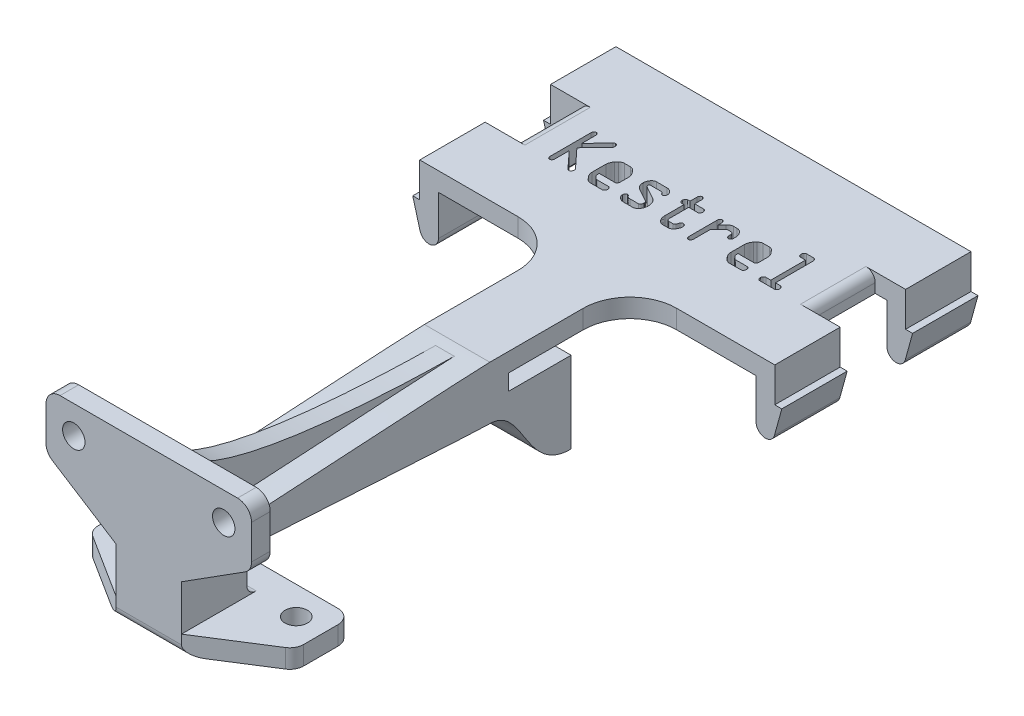
SolidWorks part; units mm, degrees
ref_plane "Front Plane" through (0, 0, 0) normal (0, 0, 1) x (1, 0, 0)
ref_plane "Top Plane" through (0, 0, 0) normal (0, 1, 0) x (1, 0, 0)
ref_plane "Right Plane" through (0, 0, 0) normal (1, 0, 0) x (0, 0, -1)
sketch "Sketch1" plane through (0, 0, 0) normal (0, 1, 0) x (1, 0, 0)
  line L0 (-19, 0) -> (-8.5, 0)
  line L1 (-19, 0) -> (-19, 5)
  line L2 (-19, 5) -> (19, 5)
  line L3 (19, 5) -> (19, 0)
  line L4 (0, 0) -> (0, -8) construction
  line L5 (0, -8) -> (0, -15) construction
  line L6 (-3.5, -15) -> (3.5, -15)
  line L7 (-3.5, -15) -> (-3.5, -5)
  line L8 (3.5, -15) -> (3.5, -5)
  line L9 (8.5, 0) -> (19, 0)
  arc A0 (3.5, -5) -> (8.5, 0) centre (8.5, -5) cw
  arc A1 (-3.5, -5) -> (-8.5, 0) centre (-8.5, -5) ccw
  point P4 (0, 0)
  point P14 (0, -15)
  point P17 (3.5, 0)
  dimension "D1" = 5
extrude "Boss-Extrude1" add sketch "Sketch1" along normal blind 2
sketch "Sketch2" plane through (0, 0, 0) normal (0, -1, 0) x (1, 0, 0)
  line L0 (-3.5, 15) -> (3.5, 15)
  line L1 (3.5, 15) -> (3.5, 13)
  line L2 (3.5, 15) -> (3.5, 5) construction
  line L3 (3.5, 13) -> (-3.5, 13)
  line L4 (-3.5, 5) -> (-3.5, 15) construction
  line L5 (-3.5, 13) -> (-3.5, 15)
extrude "Boss-Extrude2" add sketch "Sketch2" along normal blind 1.7
sketch "Sketch3" plane through (0, -1.7, 0) normal (0, -1, 0) x (1, 0, 0)
  line L0 (-3.5, 15) -> (-3.5, 6.3)
  line L1 (-3.5, 6.3) -> (3.5, 6.3)
  line L2 (3.5, 6.3) -> (3.5, 15)
  line L3 (3.5, 15) -> (-3.5, 15)
extrude "Boss-Extrude3" add sketch "Sketch3" along normal blind 2
sketch "Sketch5" plane through (0, 0, 0) normal (0, 0, 1) x (1, 0, 0)
  line L0 (0, -3.7) -> (0, 2) construction
  line L1 (3.5, -3.7) -> (-3.5, -3.7) construction
  line L2 (-3.5, 2) -> (3.5, 2) construction
  line L3 (-19, 0) -> (-19, -1.7)
  line L4 (-19, -1.7) -> (-19.75, -1.7)
  line L5 (-19, 0) -> (-17, 0)
  line L6 (-19, 0) -> (-8.5, 0) construction
  line L7 (-17, 0) -> (-17, -4.2915)
  line L9 (-19.75, -1.7) -> (-18.9642, -4.5567)
  line L10 (19.75, -1.7) -> (18.9642, -4.5567)
  line L11 (17, 0) -> (17, -4.2915)
  line L12 (19, 0) -> (17, 0)
  line L13 (19, -1.7) -> (19.75, -1.7)
  line L14 (19, 0) -> (19, -1.7)
  arc A0 (-17, -4.2915) -> (-18.9642, -4.5567) centre (-18, -4.2915) cw
  arc A1 (17, -4.2915) -> (18.9642, -4.5567) centre (18, -4.2915) ccw
  dimension "D1" = 1
extrude "Boss-Extrude5" add sketch "Sketch5" against normal up to surface (5 mm away) up to face at (0, 1, -5)
sketch "Sketch12" plane through (-3.5, 0, 0) normal (-1, 0, 0) x (0, 0, 1)
  line L0 (15, 2) -> (15, -3.7)
  line L1 (15, -0.85) -> (48, -0.85) construction
  line L2 (48, -1.85) -> (48, 0.15)
  line L5 (5, 2) -> (15, 2) construction
  line L6 (5, 2) -> (15, 2) construction
  line L7 (48, 0.15) -> (51.4434, 0.15) construction
  spline S0 degree 3 poles (48, 0.15) (45.4313, 0.15) (17.4134, 2) (15, 2) knots 0 0 0 0 1 1 1 1
  spline S1 degree 3 poles (48, -1.85) (45.4313, -1.85) (17.4134, -3.7) (15, -3.7) knots 0 0 0 0 1 1 1 1
  point P9 (48, -0.85)
extrude "Boss-Extrude10" add sketch "Sketch12" against normal up to surface (7 mm away) contours S0 L0 S1 L2 up to face at (3.5, -0.85, 9.825)
sketch "Sketch6" plane through (0, 0, 48) normal (0, 0, 1) x (1, 0, 0)
  line L0 (0, 8.9074) -> (0, 5.9074) construction
  line L1 (-8.025, 5.9074) -> (8.025, 5.9074) construction
  line L2 (-9.5, 8.9074) -> (9.5, 8.9074)
  line L3 (-11, 7.4074) -> (-11, 3.7322)
  line L4 (-10.3035, 2.4655) -> (-3.5, -1.85)
  line L5 (-3.5, -1.85) -> (3.5, -1.85)
  line L6 (11, 7.4074) -> (11, 3.7322)
  line L7 (10.3035, 2.4655) -> (3.5, -1.85)
  line L8 (3.5, -1.85) -> (-3.5, -1.85) construction
  line L9 (-3.5, -1.85) -> (3.5, -1.85)
  line L11 (3.5, -1.85) -> (-3.5, -1.85)
  line L12 (3.5, -1.85) -> (-3.5, -1.85)
  circle A0 centre (-8.025, 5.9074) radius 1.2
  circle A1 centre (8.025, 5.9074) radius 1.2
  arc A2 (11, 3.7322) -> (10.3035, 2.4655) centre (9.5, 3.7322) cw
  arc A3 (9.5, 8.9074) -> (11, 7.4074) centre (9.5, 7.4074) cw
  arc A4 (-9.5, 8.9074) -> (-11, 7.4074) centre (-9.5, 7.4074) ccw
  arc A5 (-11, 3.7322) -> (-10.3035, 2.4655) centre (-9.5, 3.7322) ccw
  point P5 (0, 5.9074)
  point P12 (0, 8.9074)
  dimension "D1" = 1.5
extrude "Boss-Extrude6" add sketch "Sketch6" against normal blind 2 contours L3 A5 L4 L7 A2 L6 A3 L2 A4 A0 A1 region at (0, 4.1004, 48)
sketch "Sketch8" plane through (0, 0, 0) normal (1, 0, 0) x (0, 0, -1)
  line L0 (-48, -1.85) -> (-17.2473, -11.6027)
sketch3d "3DSketch2"
  line L0 (3.5, -1.85, 48) -> (-3.5, -1.85, 48) construction
  line L1 (0, -1.85, 48) -> (0, -11.6027, 17.2473) construction
sketch "Sketch9" plane through (0, -29.0291, -37.7024) normal (0, 0.9532, -0.3023) x (1, 0, 0)
  line L0 (0, -51.7402) -> (0, -54.7402) construction
  line L1 (-8.025, -54.7402) -> (8.025, -54.7402) construction
  line L2 (-9.5, -51.7402) -> (9.5, -51.7402)
  line L3 (-11, -53.2402) -> (-11, -56.9154)
  line L4 (-10.3035, -58.182) -> (-3.5, -62.4976)
  line L5 (-3.5, -62.4976) -> (3.5, -62.4976)
  line L6 (11, -53.2402) -> (11, -56.9154)
  line L7 (10.3035, -58.182) -> (3.5, -62.4976)
  line L8 (3.5, -89.9089) -> (-3.5, -89.9089) construction
  line L9 (-3.5, -57.2253) -> (3.5, -57.2253) construction
  line L10 (0, -57.2253) -> (0, -62.4976) construction
  line L11 (3.5, -62.4976) -> (-3.5, -62.4976) construction
  line L12 (3.5, -89.9089) -> (-3.5, -89.9089)
  line L13 (-3.5, -62.4976) -> (3.5, -62.4976)
  circle A0 centre (-8.025, -54.7402) radius 1.2
  circle A1 centre (8.025, -54.7402) radius 1.2
  arc A2 (11, -56.9154) -> (10.3035, -58.182) centre (9.5, -56.9154) cw
  arc A3 (9.5, -51.7402) -> (11, -53.2402) centre (9.5, -53.2402) cw
  arc A4 (-9.5, -51.7402) -> (-11, -53.2402) centre (-9.5, -53.2402) ccw
  arc A5 (-11, -56.9154) -> (-10.3035, -58.182) centre (-9.5, -56.9154) ccw
  point P5 (0, -54.7402)
  point P12 (0, -51.7402)
  point P30 (0, -62.4976)
  dimension "D1" = 1.5
extrude "Boss-Extrude8" [suppressed] add sketch "Sketch9" along normal blind 2 contours A5 L3 A4 L2 A3 L6 A2 L7 L5 L4 A0 A1
sketch "Sketch11" plane through (0, 0, -5) normal (0, 0, -1) x (-1, 0, 0)
  line L10 (-19, 2) -> (-19, -1.7)
  line L11 (-19, -1.7) -> (-19.75, -1.7)
  line L12 (-19.75, -1.7) -> (-18.9642, -4.5567)
  line L13 (-17, -4.2915) -> (-17, 0)
  line L14 (-17, 0) -> (17, 0)
  line L15 (17, 0) -> (17, -4.2915)
  line L16 (18.9642, -4.5567) -> (19.75, -1.7)
  line L17 (19.75, -1.7) -> (19, -1.7)
  line L18 (19, -1.7) -> (19, 2)
  line L19 (19, 2) -> (-19, 2)
  line L20 (-19, 2) -> (-19, -1.7)
  line L21 (-19, -1.7) -> (-19.75, -1.7)
  line L22 (-19.75, -1.7) -> (-18.9642, -4.5567)
  line L23 (-17, -4.2915) -> (-17, 0)
  line L24 (-17, 0) -> (17, 0)
  line L25 (17, 0) -> (17, -4.2915)
  line L26 (18.9642, -4.5567) -> (19.75, -1.7)
  line L27 (19.75, -1.7) -> (19, -1.7)
  line L28 (19, -1.7) -> (19, 2)
  line L29 (19, 2) -> (-19, 2)
  arc A2 (-18.9642, -4.5567) -> (-17, -4.2915) centre (-18, -4.2915) ccw
  arc A3 (17, -4.2915) -> (18.9642, -4.5567) centre (18, -4.2915) ccw
  arc A4 (-18.9642, -4.5567) -> (-17, -4.2915) centre (-18, -4.2915) ccw
  arc A5 (17, -4.2915) -> (18.9642, -4.5567) centre (18, -4.2915) ccw
  dimension "D1" = 0
extrude "Boss-Extrude9" add sketch "Sketch11" along normal blind 5
sketch "Sketch13" plane through (0, 0, -10) normal (0, 0, -1) x (-1, 0, 0)
  line L0 (-17, 0) -> (-17, 2)
  line L1 (17, 0) -> (17, 2)
  line L2 (-17, 2) -> (-19, 2)
  line L10 (19, 2) -> (-19, 2)
  line L11 (-19, 2) -> (-19, -1.7)
  line L12 (-19, -1.7) -> (-19.75, -1.7)
  line L13 (-19.75, -1.7) -> (-18.9642, -4.5567)
  line L14 (-17, -4.2915) -> (-17, 0)
  line L15 (-17, 0) -> (17, 0)
  line L16 (17, 0) -> (17, -4.2915)
  line L17 (18.9642, -4.5567) -> (19.75, -1.7)
  line L18 (19.75, -1.7) -> (19, -1.7)
  line L19 (19, -1.7) -> (19, 2)
  line L20 (19, 2) -> (17, 2)
  line L21 (-19, 2) -> (-19, -1.7)
  line L22 (-19, -1.7) -> (-19.75, -1.7)
  line L23 (-19.75, -1.7) -> (-18.9642, -4.5567)
  line L24 (-17, -4.2915) -> (-17, 0)
  line L26 (17, 0) -> (17, -4.2915)
  line L27 (18.9642, -4.5567) -> (19.75, -1.7)
  line L28 (19.75, -1.7) -> (19, -1.7)
  line L29 (19, -1.7) -> (19, 2)
  arc A2 (-18.9642, -4.5567) -> (-17, -4.2915) centre (-18, -4.2915) ccw
  arc A3 (17, -4.2915) -> (18.9642, -4.5567) centre (18, -4.2915) ccw
  arc A4 (-18.9642, -4.5567) -> (-17, -4.2915) centre (-18, -4.2915) ccw
  arc A5 (17, -4.2915) -> (18.9642, -4.5567) centre (18, -4.2915) ccw
  dimension "D1" = 0
extrude "Boss-Extrude11" add sketch "Sketch13" along normal blind 11
sketch "Sketch14" [suppressed] plane through (0, 0, 0) normal (1, 0, 0) x (0, 0, -1)
  line L0 (-21.4898, -4.5318) -> (-16.4946, -9.5269) construction
  line L2 (-19.0398, -6.9817) -> (-21.6386, -4.383) construction
  line L4 (-25, 3.9255) -> (-25, 7.5698) construction
  line L6 (-25, 9.4074) -> (-25, 5.7322) construction
  line L8 (-21.4898, -4.5318) -> (-23.7806, -2.241)
  line L9 (-23.7806, -2.241) -> (-20.5918, -2.8431)
  line L10 (-25, 3.9255) -> (-25, 0.342)
  line L51 (-25, 0.342) -> (-21.429, 0.9803)
  arc A0 (-21.429, 0.9803) -> (-25, 3.9255) centre (-22, 3.9255) cw
  arc A1 (-21.4898, -4.5318) -> (-20.5918, -2.8431) centre (-20.7827, -3.8247) cw
  spline S0 degree 3 poles (2744.4383, -1158.1805) (-2916.1759, 1174.945) (2874.0779, -1177.5151) (-2786.653, 1143.8803) knots -6.32124 -6.32124 -6.32124 -6.32124 7.304164 7.304164 7.304164 7.304164 only from (-23.7806, -2.241) to (-15, -3.7) construction
  spline S1 degree 3 poles (-2786.706, -1145.6021) (2873.7453, 1175.6786) (-2915.4391, -1176.3458) (2743.3321, 1156.0245) knots -6.104431 -6.104431 -6.104431 -6.104431 7.520128 7.520128 7.520128 7.520128 only from (-15, 2) to (-25, 0.342) construction
  spline S2 degree 3 poles (-20.5918, -2.8431) (-18.3357, -3.2818) (-16.1475, -3.7) (-15, -3.7) knots 0.524559 0.524559 0.524559 0.524559 1 1 1 1 construction
  spline S3 degree 3 poles (-15, 2) (-16.2892, 2) (-18.8922, 1.4721) (-21.429, 0.9803) knots 0.199776 0.199776 0.199776 0.199776 0.733944 0.733944 0.733944 0.733944 construction
  dimension "D1" = 3
  dimension "D2" = 1
extrude "Boss-Extrude12" [suppressed] add sketch "Sketch14" along normal blind 1 and the other way blind 1 contours L51 A0 L10 | L8 A1 L9
fillet "Fillet1" [suppressed] radius 3
sketch "Sketch18" plane through (0, 0, 0) normal (1, 0, 0) x (0, 0, -1)
  line L0 (-46, 8.8773) -> (-46, 16.5411)
  line L1 (-11.8658, 2) -> (-3.0432, 2.4583)
  line L2 (-46, 8.8773) -> (-46, 0.2267)
  line L3 (-46, 0.2267) -> (-11.8658, 2)
  line L4 (-15, 2) -> (-5, 2) construction
  spline S0 degree 3 poles (-46, 8.8773) (-46, 2.0485) (-16.5023, 1.7591) (-11.8658, 2) knots 0 0 0 0 1 1 1 1
  point P0 (-11.8658, 2)
  point P5 (-46, 0.2267)
extrude "Boss-Extrude16" add sketch "Sketch18" along normal blind 1 and the other way blind 1 contours L2 L3 region at (0, 2.5751, 37.4544)
sketch "Sketch19" plane through (0, 0, -10) normal (0, 0, -1) x (-1, 0, 0)
  line L4 (-17, 0) -> (17, 0)
  line L5 (17, 0) -> (17, 2)
  line L6 (17, 2) -> (-17, 2)
  line L7 (-17, 2) -> (-17, 0)
  line L8 (-17, 0) -> (17, 0)
  line L9 (17, 0) -> (17, 2)
  line L10 (17, 2) -> (-17, 2)
  line L11 (-17, 2) -> (-17, 0)
  dimension "D1" = 0
extrude "Boss-Extrude17" add sketch "Sketch19" along normal up to surface (11 mm away) up to face at (18.433, -1.5178, -21)
sketch "Sketch20" plane through (0, 2, 0) normal (0, 1, 0) x (1, 0, 0)
  line L0 (-19.75, 0) -> (-19.75, 21) construction
  line L1 (19.75, 0) -> (19.75, 21) construction
  line L4 (-23.75, 14) -> (-15.75, 14)
  line L5 (-23.75, 14) -> (-23.75, 7)
  line L6 (-23.75, 7) -> (-15.75, 7)
  line L7 (-15.75, 14) -> (-15.75, 7)
  line L8 (-23.75, 14) -> (-15.75, 7) construction
  line L9 (-23.75, 7) -> (-15.75, 14) construction
  line L10 (15.75, 14) -> (23.75, 14)
  line L11 (15.75, 14) -> (15.75, 7)
  line L12 (15.75, 7) -> (23.75, 7)
  line L13 (23.75, 14) -> (23.75, 7)
  line L14 (15.75, 14) -> (23.75, 7) construction
  line L15 (15.75, 7) -> (23.75, 14) construction
  point P6 (-19.75, 10.5)
  point P15 (19.75, 10.5)
extrude "Cut-Extrude2" cut sketch "Sketch20" against normal blind 10.2
fillet "Fillet3" radius 1 2 edges at (15.75, 2, -10.5) (-15.75, 2, -10.5)
sketch "Sketch22" plane through (0, 2, 0) normal (0, 1, 0) x (1, 0, 0)
  line L0 (-15.75, 7) -> (15.75, 7) construction
  text T0 "Kestrel" font "OCR A Extended" height 5
extrude "Cut-Extrude4" cut sketch "Sketch22" against normal up to surface (2 mm away) up to face at (0, 0, -5.1151)
delete or keep bodies "Body-Delete/Keep 1" type delete bodies bodies 125 126
sketch "Sketch23" plane through (-3.5, 0, 0) normal (-1, 0, 0) x (0, 0, 1)
  line L0 (6.3, -3.7) -> (6.3, -10.4)
  line L1 (13, -3.7) -> (6.3, -3.7)
  line L2 (6.3, -10.4) -> (3.1823, -10.4) construction
  line L3 (15, -3.7) -> (6.3, -3.7) construction
  line L4 (15, -3.7) -> (6.3, -3.7) construction
  spline S0 degree 3 poles (6.3, -10.4) (9.9895, -10.4) (9.9638, -3.7) (13, -3.7) knots 0 0 0 0 1 1 1 1
extrude "Boss-Extrude18" add sketch "Sketch23" against normal up to surface (7 mm away) up to face at (3.5, -0.9374, 16.9636)
sketch "Sketch27" plane through (0, -3.7, 0) normal (0, -1, 0) x (1, 0, 0)
  line L0 (3.5, 48) -> (-3.5, 48) construction
  line L1 (3.5, 48) -> (-3.5, 48)
  line L2 (0, 37.2426) -> (0, 40.2426) construction
  line L3 (8.025, 40.2426) -> (-8.025, 40.2426) construction
  line L4 (9.5, 37.2426) -> (-9.5, 37.2426)
  line L5 (11, 38.7426) -> (11, 42.4178)
  line L6 (10.3035, 43.6845) -> (3.5, 48)
  line L7 (3.5, 48) -> (-3.5, 48)
  line L8 (-11, 38.7426) -> (-11, 42.4178)
  line L9 (-10.3035, 43.6845) -> (-3.5, 48)
  line L10 (3.5, 48) -> (-3.5, 48)
  line L11 (-3.5, 48) -> (3.5, 48)
  line L12 (-3.5, 48) -> (3.5, 48)
  line L13 (3.5, 15) -> (3.5, 48) construction
  line L14 (-3.5, 48) -> (3.5, 48)
  line L16 (-3.5, 48) -> (-3.5, 41)
  line L17 (-3.5, 41) -> (3.5, 41)
  line L18 (3.5, 48) -> (3.5, 41)
  circle A0 centre (8.025, 40.2426) radius 1.2
  circle A1 centre (-8.025, 40.2426) radius 1.2
  arc A2 (-11, 42.4178) -> (-10.3035, 43.6845) centre (-9.5, 42.4178) cw
  arc A3 (-9.5, 37.2426) -> (-11, 38.7426) centre (-9.5, 38.7426) cw
  arc A4 (9.5, 37.2426) -> (11, 38.7426) centre (9.5, 38.7426) ccw
  arc A5 (11, 42.4178) -> (10.3035, 43.6845) centre (9.5, 42.4178) ccw
  point P7 (0, 40.2426)
  point P14 (0, 37.2426)
  dimension "D1" = 1.5
extrude "Boss-Extrude21" add sketch "Sketch27" against normal blind 2 and the other way blind 3 contours L18 L1 L16 L17 region at (0, -3.7, 44.5)
sketch "Sketch28" plane through (0, -6.7, 0) normal (0, -1, 0) x (1, 0, 0)
  line L4 (3.5, 48) -> (-3.5, 48)
  line L5 (3.5, 41) -> (3.5, 48)
  line L6 (-3.5, 48) -> (-10.3035, 43.6845)
  line L7 (-11, 42.4178) -> (-11, 38.7426)
  line L8 (-9.5, 37.2426) -> (9.5, 37.2426)
  line L9 (11, 38.7426) -> (11, 42.4178)
  line L10 (10.3035, 43.6845) -> (3.5, 48)
  line L11 (3.5, 48) -> (-3.5, 48)
  line L12 (-3.5, 48) -> (-10.3035, 43.6845)
  line L13 (-11, 42.4178) -> (-11, 38.7426)
  line L14 (-9.5, 37.2426) -> (9.5, 37.2426)
  line L15 (11, 38.7426) -> (11, 42.4178)
  line L16 (10.3035, 43.6845) -> (3.5, 48)
  line L17 (3.5, 48) -> (-3.5, 48)
  line L18 (-3.5, 41) -> (3.5, 41)
  line L19 (-3.5, 48) -> (-3.5, 41)
  line L20 (3.5, 48) -> (-3.5, 48)
  circle A1 centre (-8.025, 40.2426) radius 1.2
  circle A2 centre (-8.025, 40.2426) radius 1.2
  circle A3 centre (8.025, 40.2426) radius 1.2
  circle A4 centre (8.025, 40.2426) radius 1.2
  arc A8 (-10.3035, 43.6845) -> (-11, 42.4178) centre (-9.5, 42.4178) ccw
  arc A9 (-11, 38.7426) -> (-9.5, 37.2426) centre (-9.5, 38.7426) ccw
  arc A10 (9.5, 37.2426) -> (11, 38.7426) centre (9.5, 38.7426) ccw
  arc A11 (11, 42.4178) -> (10.3035, 43.6845) centre (9.5, 42.4178) ccw
  arc A12 (-10.3035, 43.6845) -> (-11, 42.4178) centre (-9.5, 42.4178) ccw
  arc A13 (-11, 38.7426) -> (-9.5, 37.2426) centre (-9.5, 38.7426) ccw
  arc A14 (9.5, 37.2426) -> (11, 38.7426) centre (9.5, 38.7426) ccw
  arc A15 (11, 42.4178) -> (10.3035, 43.6845) centre (9.5, 42.4178) ccw
  line M17 (3.5, 41) -> (3.5, 48)
  line M18 (3.5, 48) -> (-3.5, 48)
  line M19 (-3.5, 48) -> (-3.5, 41)
  line M20 (-3.5, 41) -> (3.5, 41)
  dimension "D1" = 0
  dimension "D2" = 0
  dimension "D3" = 0
  dimension "D4" = 0
extrude "Boss-Extrude22" add sketch "Sketch28" along normal blind 2 contours L15 A15 L16 L12 A12 L13 A13 L14 A14 A2 A4 M17 M20 M19 | M20 M17 M18 M19 region at (0, -6.7, 44.5) region at (6.7706, -6.7, 45.6354)
fillet "Fillet6" radius 2 1 edges at (0, -2.2026, 41)
fillet "Fillet7" radius 1 1 edges at (0, -6.7, 41)
sketch "Sketch29" plane through (-3.5, 0, 0) normal (-1, 0, 0) x (0, 0, 1)
  line L0 (6.3, -10.4) -> (3.8714, -10.4) construction
  line L1 (6.3, -10.4) -> (6.3, -3.7)
  line L2 (6.3, -10.4) -> (6.3, -1.7) construction
  line L3 (6.3, -3.7) -> (15, -3.7)
  spline S0 degree 3 poles (15, -3.7) (11.3397, -3.7) (11.2527, -10.4) (6.3, -10.4) knots 0 0 0 0 1 1 1 1
  spline S1 degree 3 poles (38.8816, -2.3271) (29.6375, -2.8753) (16.6114, -3.7) (15, -3.7) knots 0.332311 0.332311 0.332311 0.332311 1 1 1 1 construction
extrude "Boss-Extrude23" add sketch "Sketch29" against normal up to surface (7 mm away) up to face at (3.5, -2.5073, 24.5311)
fillet "Fillet8" radius 1 1 edges at (0, -8.7, 48)
